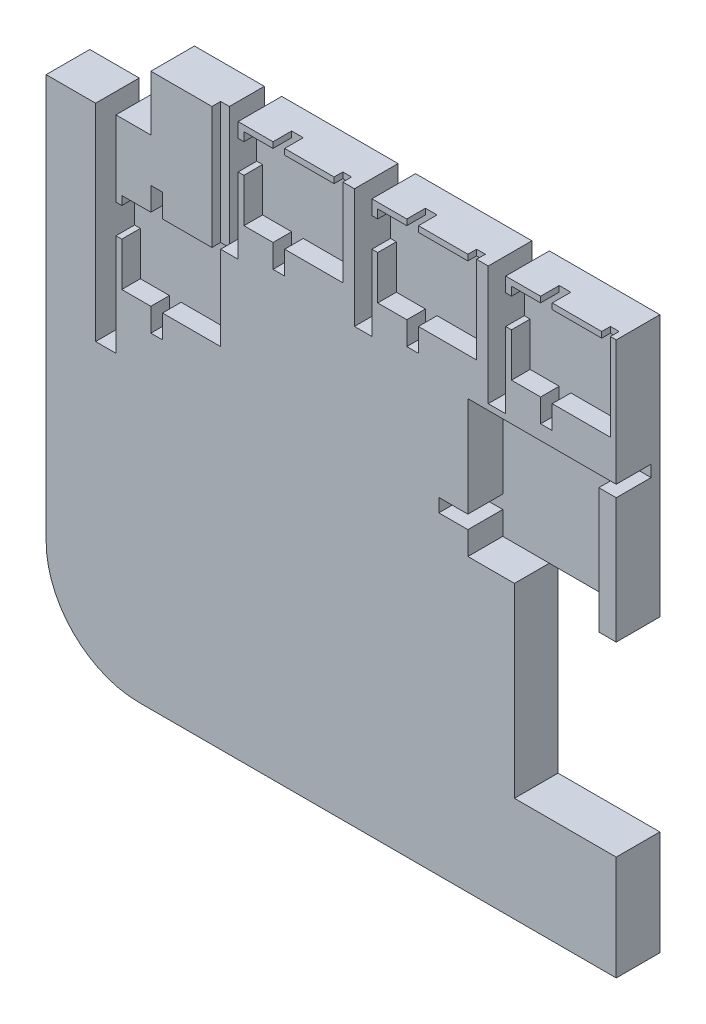
SolidWorks part; units mm, degrees
ref_plane "Front Plane" through (0, 0, 0) normal (0, 0, 1) x (1, 0, 0)
ref_plane "Top Plane" through (0, 0, 0) normal (0, 1, 0) x (1, 0, 0)
ref_plane "Right Plane" through (0, 0, 0) normal (1, 0, 0) x (0, 0, -1)
sketch "Sketch1" plane through (0, 0, 0) normal (0, 0, 1) x (1, 0, 0)
  line L1 (-33, -47.5) -> (49, -47.5)
  line L2 (-49, -31.5) -> (-49, 47.5)
  line L3 (-49, 47.5) -> (27, 47.5)
  line L4 (49, -47.5) -> (49, -29.5)
  line L5 (-49, -47.5) -> (49, 47.5) construction
  line L6 (-49, 47.5) -> (49, -47.5) construction
  line L10 (49, 2.5) -> (31.5, 2.5)
  line L11 (31.5, 2.5) -> (31.5, -29.5)
  line L12 (31.5, -29.5) -> (49, -29.5)
  line L13 (49, 2.5) -> (49, 47.5)
  line L14 (30, 47.5) -> (49, 47.5)
  line L16 (30, 47.5) -> (30, 30.5)
  line L17 (30, 30.5) -> (27, 30.5)
  line L18 (27, 47.5) -> (27, 30.5)
  arc A0 (-33, -47.5) -> (-49, -31.5) centre (-33, -31.5) cw
  point P0 (0, 0)
  point P15 (30, 39)
  dimension "D3" = 16
  dimension "D1" = 98
  dimension "D2" = 95
  dimension "D4" = 18
  dimension "D5" = 17.5
  dimension "D6" = 32
  dimension "D7" = 17
  dimension "D8" = 19
  dimension "D9" = 3
extrude "Boss-Extrude1" add sketch "Sketch1" along normal blind 7.5
sketch "Sketch2" plane through (0, 0, 7.5) normal (0, 0, 1) x (1, 0, 0)
  line L0 (30, 40) -> (31, 40)
  line L1 (30, 47.5) -> (30, 30.5) construction
  line L2 (31, 40) -> (31, 32.5)
  line L3 (31, 32.5) -> (36, 32.5)
  line L4 (36, 32.5) -> (36, 28.5)
  line L5 (36, 28.5) -> (38, 28.5)
  line L6 (38, 28.5) -> (38, 32.5)
  line L7 (38, 32.5) -> (48, 32.5)
  line L8 (48, 32.5) -> (48, 46.5)
  line L9 (48, 46.5) -> (38, 46.5)
  line L10 (31, 46.5) -> (31, 45)
  line L11 (31, 45) -> (30, 45)
  line L12 (30, 45) -> (30, 40)
  line L13 (-16, 40) -> (-15, 40)
  line L14 (36, 46.5) -> (36, 47.5)
  line L15 (49, 47.5) -> (30, 47.5) construction
  line L16 (36, 47.5) -> (38, 47.5)
  line L17 (38, 47.5) -> (38, 46.5)
  line L19 (36, 46.5) -> (31, 46.5)
  line L20 (7, 40) -> (8, 40)
  line L21 (8, 40) -> (8, 32.5)
  line L22 (8, 32.5) -> (13, 32.5)
  line L23 (13, 32.5) -> (13, 28.5)
  line L24 (13, 28.5) -> (15, 28.5)
  line L25 (15, 28.5) -> (15, 32.5)
  line L26 (15, 32.5) -> (25, 32.5)
  line L27 (25, 32.5) -> (25, 46.5)
  line L28 (25, 46.5) -> (15, 46.5)
  line L29 (8, 46.5) -> (8, 45)
  line L30 (8, 45) -> (7, 45)
  line L31 (7, 45) -> (7, 40)
  line L32 (13, 46.5) -> (13, 47.5)
  line L33 (13, 47.5) -> (15, 47.5)
  line L34 (15, 47.5) -> (15, 46.5)
  line L35 (13, 46.5) -> (8, 46.5)
  line L36 (49, 2.5) -> (49, 47.5) construction
  line L37 (27, 47.5) -> (-49, 47.5) construction
  line L38 (-15, 40) -> (-15, 32.5)
  line L39 (-15, 32.5) -> (-10, 32.5)
  line L40 (-10, 32.5) -> (-10, 28.5)
  line L41 (-10, 28.5) -> (-8, 28.5)
  line L42 (-8, 28.5) -> (-8, 32.5)
  line L43 (-8, 32.5) -> (2, 32.5)
  line L44 (2, 32.5) -> (2, 46.5)
  line L45 (2, 46.5) -> (-8, 46.5)
  line L46 (-15, 46.5) -> (-15, 45)
  line L47 (-15, 45) -> (-16, 45)
  line L48 (-16, 45) -> (-16, 40)
  line L49 (-10, 46.5) -> (-10, 47.5)
  line L50 (-10, 47.5) -> (-8, 47.5)
  line L51 (-8, 47.5) -> (-8, 46.5)
  line L52 (-10, 46.5) -> (-15, 46.5)
  point P4 (30, 42.5)
  dimension "D1" = 1
  dimension "D2" = 5
  dimension "D3" = 5
  dimension "D4" = 4
  dimension "D5" = 17
  dimension "D6" = 10
  dimension "D7" = 2
  dimension "D8" = 4
  dimension "D9" = 14
  dimension "D10" = 24
  dimension "D11" = 1
  dimension "D12" = 6
extrude "Cut-Extrude1" cut sketch "Sketch2" against normal blind 3.2
sketch "Sketch3" plane through (0, -47.5, 0) normal (0, -1, 0) x (1, 0, 0)
  line L0 (-33, 7.5) -> (49, 7.5) construction
  line L2 (49, 7.5) -> (31.5, 7.5) construction
  line L4 (34.25, 7.5) -> (46.25, 7.5)
  arc A0 (46.25, 7.5) -> (34.25, 7.5) centre (40.25, 7.5) cw
  point P6 (40.25, 7.5)
  dimension "D2" = 6
  dimension "D1" = 17.5
sketch "Sketch5" plane through (0, 0, 7.5) normal (0, 0, 1) x (1, 0, 0)
  line L0 (7, 47.5) -> (7, 30.5)
  line L1 (13, 47.5) -> (-8, 47.5) construction
  line L2 (7, 30.5) -> (4, 30.5)
  line L3 (4, 30.5) -> (4, 47.5)
  line L4 (4, 47.5) -> (7, 47.5)
  line L5 (27, 30.5) -> (27, 47.5) construction
  line L6 (30, 30.5) -> (27, 30.5) construction
  line L7 (7, 45) -> (7, 40) construction
  line L8 (-16, 47.5) -> (-16, 30.5)
  line L9 (-10, 47.5) -> (-49, 47.5) construction
  line L10 (-16, 30.5) -> (-19, 30.5)
  line L11 (-19, 30.5) -> (-19, 47.5)
  line L12 (-19, 47.5) -> (-16, 47.5)
  line L13 (-16, 45) -> (-16, 40) construction
extrude "Cut-Extrude4" cut sketch "Sketch5" against normal up to next
sketch "Sketch8" plane through (0, 0, 7.5) normal (0, 0, 1) x (1, 0, 0)
  line L0 (-19, 47.5) -> (-49, 47.5) construction
  line L1 (-37, 47.5) -> (-49, 47.5)
  line L2 (-37, 47.5) -> (-37, 10.5)
  line L3 (-37, 10.5) -> (-49, 10.5)
  line L4 (-49, 47.5) -> (-49, 10.5)
  line L5 (-49, 47.5) -> (-49, -31.5) construction
  dimension "D1" = 12
  dimension "D2" = 37
extrude "Cut-Extrude5" cut sketch "Sketch8" against normal up to next
sketch "Sketch9" plane through (0, 0, 7.5) normal (0, 0, 1) x (1, 0, 0)
  line L0 (-37, 20) -> (-36, 20)
  line L1 (-36, 20) -> (-36, 12.5)
  line L2 (-36, 12.5) -> (-31, 12.5)
  line L3 (-31, 12.5) -> (-31, 8.5)
  line L4 (-31, 8.5) -> (-29, 8.5)
  line L5 (-29, 8.5) -> (-29, 12.5)
  line L6 (-29, 12.5) -> (-19, 12.5)
  line L7 (-19, 12.5) -> (-19, 26.5)
  line L8 (-19, 26.5) -> (-29, 26.5)
  line L9 (-36, 26.5) -> (-36, 25)
  line L10 (-36, 25) -> (-37, 25)
  line L11 (-37, 25) -> (-37, 20)
  line L12 (-31, 26.5) -> (-31, 30.5)
  line L13 (-31, 30.5) -> (-29, 30.5)
  line L14 (-29, 30.5) -> (-29, 26.5)
  line L15 (-31, 26.5) -> (-36, 26.5)
  line L16 (-49, 10.5) -> (-37, 10.5) construction
  line L17 (-37, 10.5) -> (-37, 47.5) construction
  point P2 (-37, 22.5)
  dimension "D1" = 14
  dimension "D2" = 17
  dimension "D3" = 10
  dimension "D4" = 2
  dimension "D5" = 5
  dimension "D6" = 4
  dimension "D7" = 7.5
  dimension "D8" = 5
  dimension "D9" = 1
  dimension "D10" = 4
  dimension "D11" = 12
extrude "Cut-Extrude6" cut sketch "Sketch9" against normal blind 3.2
sketch "Sketch10" plane through (0, 10.5, 0) normal (0, 1, 0) x (1, 0, 0)
  line L0 (-49, -7.5) -> (-37, -7.5) construction
  line L1 (-49, 0) -> (-39, 0)
  line L2 (-49, 0) -> (-49, -7.5)
  line L3 (-49, -7.5) -> (-39, -7.5)
  line L4 (-39, 0) -> (-39, -7.5)
  dimension "D1" = 10
extrude "Boss-Extrude2" add sketch "Sketch10" along normal blind 27.4864
sketch "Sketch11" plane through (0, 30.5, 0) normal (0, 1, 0) x (1, 0, 0)
  line L1 (-19, 0) -> (-16, 0)
  line L2 (-19, 0) -> (-19, -7.5)
  line L3 (-19, -7.5) -> (-16, -7.5)
  line L4 (-16, 0) -> (-16, -7.5)
  line L5 (4, 0) -> (7, 0)
  line L6 (4, 0) -> (4, -7.5)
  line L7 (4, -7.5) -> (7, -7.5)
  line L8 (7, 0) -> (7, -7.5)
  line L9 (27, 0) -> (30, 0)
  line L10 (27, 0) -> (27, -7.5)
  line L11 (27, -7.5) -> (30, -7.5)
  line L12 (30, 0) -> (30, -7.5)
extrude "Cut-Extrude7" cut sketch "Sketch11" against normal blind 3.5
sketch "Sketch12" plane through (0, 10.5, 0) normal (0, 1, 0) x (1, 0, 0)
  line L1 (-37, 0) -> (-39, 0)
  line L2 (-37, 0) -> (-37, -7.5)
  line L3 (-37, -7.5) -> (-39, -7.5)
  line L4 (-39, 0) -> (-39, -7.5)
extrude "Cut-Extrude8" cut sketch "Sketch12" against normal blind 4
sketch "Sketch13" plane through (0, 6.5, 0) normal (0, 1, 0) x (1, 0, 0)
  line L1 (-39, 0) -> (-37, 0)
  line L2 (-39, 0) -> (-39, -7.5)
  line L3 (-39, -7.5) -> (-37, -7.5)
  line L4 (-37, 0) -> (-37, -7.5)
extrude "Cut-Extrude9" cut sketch "Sketch13" against normal blind 4
sketch "Sketch14" plane through (-37, 0, 0) normal (-1, 0, 0) x (0, 0, 1)
  line L0 (7.5, 25) -> (7.5, 47.5) construction
  line L1 (0, 47.5) -> (7.5, 47.5)
  line L2 (0, 47.5) -> (0, 38)
  line L3 (0, 38) -> (7.5, 38)
  line L4 (7.5, 47.5) -> (7.5, 38)
  dimension "D1" = 13
extrude "Cut-Extrude10" cut sketch "Sketch14" against normal blind 6
sketch "Sketch15" plane through (0, 0, 7.5) normal (0, 0, 1) x (1, 0, 0)
  line L0 (-19, 26.5) -> (-29, 26.5) construction
  line L1 (-19, 47.5) -> (-20.5, 47.5)
  line L2 (-19, 47.5) -> (-19, 26.5)
  line L3 (-19, 26.5) -> (-20.5, 26.5)
  line L4 (-20.5, 47.5) -> (-20.5, 26.5)
  line L5 (4, 47.5) -> (-8, 47.5) construction
  line L6 (2, 46.5) -> (0.5, 46.5)
  line L7 (2, 46.5) -> (2, 47.5)
  line L8 (2, 47.5) -> (0.5, 47.5)
  line L9 (0.5, 46.5) -> (0.5, 47.5)
  line L10 (27, 47.5) -> (15, 47.5) construction
  line L11 (25, 46.5) -> (23.5, 46.5)
  line L12 (25, 46.5) -> (25, 47.5)
  line L13 (25, 47.5) -> (23.5, 47.5)
  line L14 (23.5, 46.5) -> (23.5, 47.5)
  line L15 (49, 47.5) -> (38, 47.5) construction
  line L16 (48, 46.5) -> (46.5, 46.5)
  line L17 (48, 46.5) -> (48, 47.5)
  line L18 (48, 47.5) -> (46.5, 47.5)
  line L19 (46.5, 46.5) -> (46.5, 47.5)
  dimension "D1" = 1.5
  dimension "D2" = 1.5
  dimension "D3" = 1.5
  dimension "D4" = 1.5
extrude "Cut-Extrude11" cut sketch "Sketch15" against normal blind 1.5
ref_plane "Plane1" through (0, 0, 17.5) normal (0, 0, 1) x (1, 0, 0)
sketch "Sketch16" plane through (0, 37.9864, 0) normal (0, 1, 0) x (1, 0, 0)
  line L0 (-39, 0) -> (-49, 0) construction
  line L1 (-40.5, 0) -> (-39, 0)
  line L2 (-40.5, 0) -> (-40.5, -7.5)
  line L3 (-40.5, -7.5) -> (-39, -7.5)
  line L4 (-39, 0) -> (-39, -7.5)
  line L5 (-49, -7.5) -> (-39, -7.5) construction
  line L6 (-49, 0) -> (-49, -7.5) construction
  dimension "D1" = 8.5
  dimension "D2" = 10
extrude "Cut-Extrude12" cut sketch "Sketch16" against normal blind 35.4864
sketch "Sketch18" plane through (0, 0, 7.5) normal (0, 0, 1) x (1, 0, 0)
  line L0 (23.5, 6.5) -> (23.5, 2.5)
  line L1 (23.5, 26) -> (46, 26)
  line L2 (23.5, 26) -> (23.5, 8.8)
  line L3 (23.5, 2.5) -> (46, 2.5)
  line L4 (46, 24) -> (46, 2.5)
  line L5 (23.5, 6.5) -> (18.5, 6.5)
  line L7 (23.5, 8.8) -> (18.5, 8.8)
  line L8 (18.5, 6.5) -> (18.5, 8.8)
  line L9 (49, 2.5) -> (49, 47.5) construction
  line L10 (31.5, 2.5) -> (49, 2.5) construction
  line L12 (46, 26) -> (49, 26)
  line L14 (46, 24) -> (49, 24)
  line L15 (49, 26) -> (49, 24)
  point P5 (23.5, 6.5)
  dimension "D1" = 22.5
  dimension "D2" = 23.5
  dimension "D3" = 4
  dimension "D4" = 5
  dimension "D5" = 2.3
  dimension "D6" = 3
  dimension "D7" = 2
  dimension "D8" = 22.5
extrude "Cut-Extrude13" cut sketch "Sketch18" against normal blind 6
